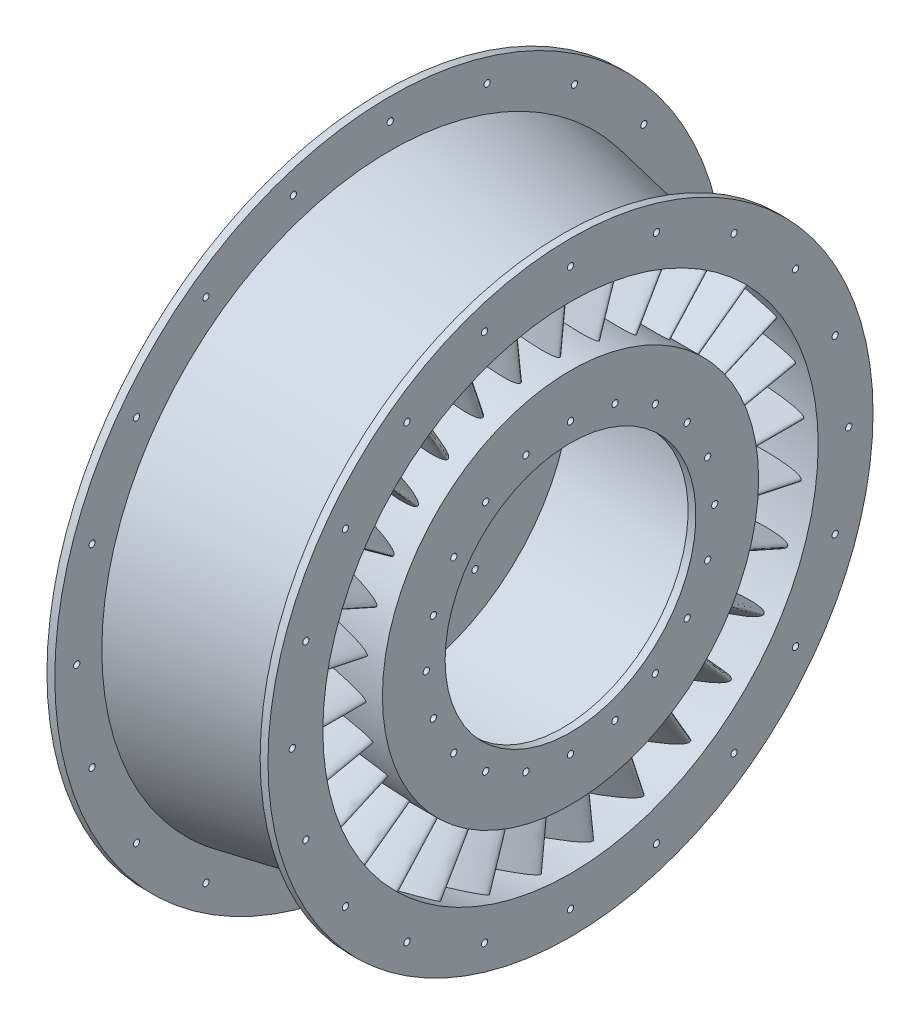
SolidWorks part; units mm, degrees
ref_plane "Front Plane" through (0, 0, 0) normal (0, 0, 1) x (1, 0, 0)
ref_plane "Top Plane" through (0, 0, 0) normal (0, 1, 0) x (1, 0, 0)
ref_plane "Right Plane" through (0, 0, 0) normal (1, 0, 0) x (0, 0, -1)
sketch "Sketch1" plane through (0, 0, 0) normal (0, 0, 1) x (1, 0, 0)
  line L0 (60, 120) -> (60, 80)
  line L1 (60, 120) -> (-60, 120)
  line L2 (-60, 120) -> (-60, 80)
  line L3 (60, 80) -> (55, 80)
  line L4 (55, 80) -> (55, 115)
  line L5 (-60, 80) -> (-55, 80)
  line L6 (-55, 80) -> (-55, 115)
  line L7 (-55, 115) -> (55, 115)
  line L8 (60, 193) -> (55, 193)
  line L9 (60, 158) -> (60, 193)
  line L10 (-60, 179) -> (60, 158)
  line L11 (55, 193) -> (55, 163)
  line L12 (-60, 214) -> (-55, 214)
  line L13 (-55, 214) -> (-55, 184)
  line L14 (55, 163) -> (-55, 184)
  line L15 (-60, 214) -> (-60, 179)
  line L16 (-71.7543, 0) -> (79.4267, 0) construction
  dimension "D1" = 120
  dimension "D2" = 5
  dimension "D3" = 80
  dimension "D4" = 120
  dimension "D5" = 158
  dimension "D6" = 193
  dimension "D7" = 214
revolve "Revolve1" add sketch "Sketch1" angle 360 about L16
sketch "Sketch2" plane through (0, 0, 0) normal (0, 0, 1) x (1, 0, 0)
  line L0 (-282.3219, 0) -> (269.1907, 0) construction
  line L1 (0, 0) -> (49.2404, -8.6824) construction
  ellipse E0 centre (0, 0) end of major axis (-49.2404, 8.6824) minor radius 6
  dimension "D1" = 100
  dimension "D2" = 6
  dimension "D3" = 10
extrude "Boss-Extrude1" add sketch "Sketch2" along normal up to surface (61.9041 mm away) from offset 115 up to face at (60, 0, 158)
pattern_circular "CirPattern1" count 30 over 360 about axis through (-60, 0, 0) along (-1, 0, 0) of "Boss-Extrude1"
sketch "Sketch3" plane through (-60, 0, 0) normal (-1, 0, 0) x (0, 0, 1)
  circle A0 centre (0, 200) radius 2
  circle A1 centre (0, 92) radius 2
  circle A2 centre (61.8034, 190.2113) radius 2
  circle A3 centre (28.4296, 87.4972) radius 2
  circle A4 centre (117.5571, 161.8034) radius 2
  circle A5 centre (54.0762, 74.4296) radius 2
  circle A6 centre (161.8034, 117.5571) radius 2
  circle A7 centre (74.4296, 54.0762) radius 2
  circle A8 centre (190.2113, 61.8034) radius 2
  circle A9 centre (87.4972, 28.4296) radius 2
  circle A10 centre (200, 0) radius 2
  circle A11 centre (92, 0) radius 2
  circle A12 centre (190.2113, -61.8034) radius 2
  circle A13 centre (87.4972, -28.4296) radius 2
  circle A14 centre (161.8034, -117.5571) radius 2
  circle A15 centre (74.4296, -54.0762) radius 2
  circle A16 centre (117.5571, -161.8034) radius 2
  circle A17 centre (54.0762, -74.4296) radius 2
  circle A18 centre (61.8034, -190.2113) radius 2
  circle A19 centre (28.4296, -87.4972) radius 2
  circle A20 centre (0, -200) radius 2
  circle A21 centre (0, -92) radius 2
  circle A22 centre (-61.8034, -190.2113) radius 2
  circle A23 centre (-28.4296, -87.4972) radius 2
  circle A24 centre (-117.5571, -161.8034) radius 2
  circle A25 centre (-54.0762, -74.4296) radius 2
  circle A26 centre (-161.8034, -117.5571) radius 2
  circle A27 centre (-74.4296, -54.0762) radius 2
  circle A28 centre (-190.2113, -61.8034) radius 2
  circle A29 centre (-87.4972, -28.4296) radius 2
  circle A30 centre (-200, 0) radius 2
  circle A31 centre (-92, 0) radius 2
  circle A32 centre (-190.2113, 61.8034) radius 2
  circle A33 centre (-87.4972, 28.4296) radius 2
  circle A34 centre (-161.8034, 117.5571) radius 2
  circle A35 centre (-74.4296, 54.0762) radius 2
  circle A36 centre (-117.5571, 161.8034) radius 2
  circle A37 centre (-54.0762, 74.4296) radius 2
  circle A38 centre (-61.8034, 190.2113) radius 2
  circle A39 centre (-28.4296, 87.4972) radius 2
  point P84 (0, 0)
  dimension "D1" = 200
  dimension "D2" = 92
  dimension "D3" = 20
extrude "Cut-Extrude1" cut sketch "Sketch3" against normal through all
sketch "Sketch4" plane through (60, 0, 0) normal (1, 0, 0) x (0, 0, -1)
  circle A0 centre (0, 177.5) radius 2
  circle A1 centre (54.8505, 168.8125) radius 2
  circle A2 centre (104.3319, 143.6005) radius 2
  circle A3 centre (143.6005, 104.3319) radius 2
  circle A4 centre (168.8125, 54.8505) radius 2
  circle A5 centre (177.5, 0) radius 2
  circle A6 centre (168.8125, -54.8505) radius 2
  circle A7 centre (143.6005, -104.3319) radius 2
  circle A8 centre (104.3319, -143.6005) radius 2
  circle A9 centre (54.8505, -168.8125) radius 2
  circle A10 centre (0, -177.5) radius 2
  circle A11 centre (-54.8505, -168.8125) radius 2
  circle A12 centre (-104.3319, -143.6005) radius 2
  circle A13 centre (-143.6005, -104.3319) radius 2
  circle A14 centre (-168.8125, -54.8505) radius 2
  circle A15 centre (-177.5, 0) radius 2
  circle A16 centre (-168.8125, 54.8505) radius 2
  circle A17 centre (-143.6005, 104.3319) radius 2
  circle A18 centre (-104.3319, 143.6005) radius 2
  circle A19 centre (-54.8505, 168.8125) radius 2
  point P44 (0, 0)
  dimension "D1" = 177.5
  dimension "D2" = 20
extrude "Cut-Extrude2" cut sketch "Sketch4" against normal blind 5
sketch "Sketch5" plane through (-60, 0, 0) normal (-1, 0, 0) x (0, 0, 1)
  circle A0 centre (28.4296, 87.4972) radius 2 construction
  circle A1 centre (28.4296, 87.4972) radius 2
extrude "Boss-Extrude2" add sketch "Sketch5" against normal up to surface (5 mm away) up to face at (-55, 87.4972, -26.4296)
pattern_circular "CirPattern2" count 10 over 360 about axis through (-60, 0, 0) along (-1, 0, 0) of "Boss-Extrude2"
